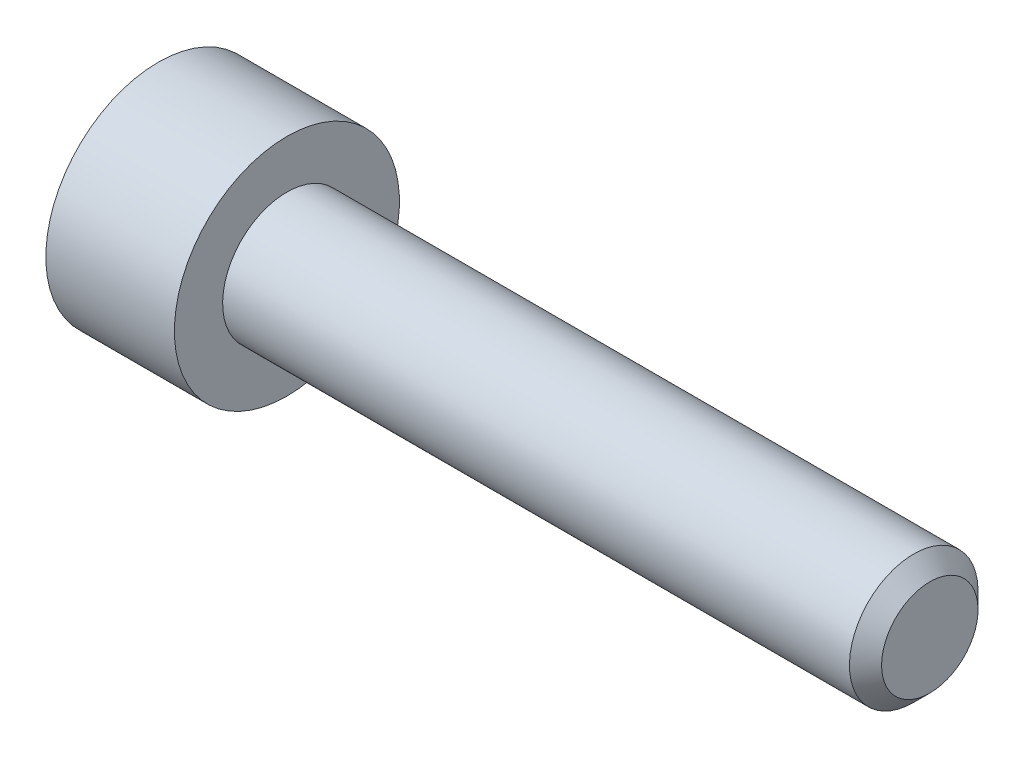
SolidWorks part; units mm, degrees
material "市購件"
ref_plane "前基準面" through (0, 0, 0) normal (0, 0, 1) x (1, 0, 0)
ref_plane "上基準面" through (0, 0, 0) normal (0, 1, 0) x (1, 0, 0)
ref_plane "右基準面" through (0, 0, 0) normal (1, 0, 0) x (0, 0, -1)
sketch "草圖1" plane through (0, 0, 0) normal (0, 0, 1) x (1, 0, 0)
  line L0 (-4, 0) -> (-4, 3.5)
  line L1 (-4, 3.5) -> (0, 3.5)
  line L2 (0, 3.5) -> (0, 2)
  line L3 (0, 2) -> (19.5, 2)
  line L4 (19.5, 2) -> (20, 1.5)
  line L5 (20, 1.5) -> (20, 0)
  line L6 (20, 0) -> (-4, 0)
  line L7 (20, 0) -> (-4, 0) construction
  dimension "D1" = 0.5
  dimension "D2" = 0.5
  dimension "D3" = 20
revolve "旋轉1" add sketch "草圖1" angle 360 about L7 reverse direction yes
cosmetic thread "裝飾螺紋線1" parameters "D2"=3.141
sketch "草圖2" plane through (0, 0, 0) normal (0, 0, 1) x (1, 0, 0)
  line L0 (-4, 0) -> (-4, 1.5)
  line L1 (-4, 1.5) -> (-2, 1.5)
  line L2 (-2, 1.5) -> (-1.5981, 0)
  line L3 (-1.5981, 0) -> (-4, 0)
  line L4 (-1.5981, 0) -> (-4, 0) construction
revolve "除料-旋轉1" cut sketch "草圖2" angle 360 about L4 reverse direction yes
ref_plane "平面1" through (-4, 0, 0) normal (1, 0, 0) x (0, 0, -1)
sketch "草圖3" plane through (-4, 0, 0) normal (1, 0, 0) x (0, 0, -1)
  line L0 (-1.5, 0.866) -> (-1.5, -0.866)
  line L1 (-1.5, -0.866) -> (0, -1.7321)
  line L2 (0, -1.7321) -> (1.5, -0.866)
  line L3 (1.5, -0.866) -> (1.5, 0.866)
  line L4 (1.5, 0.866) -> (0, 1.7321)
  line L5 (0, 1.7321) -> (-1.5, 0.866)
extrude "除料-伸長1" cut sketch "草圖3" along normal blind 2
ref_plane "平面2" through (16, 0, 0) normal (1, 0, 0) x (0, 0, -1)
ref_plane "screw1 XY" through (0, 0, 0) normal (1, 0, 0) x (0, 0, -1)
ref_plane "screw1 XZ" through (0, 0, 0) normal (0, -1, 0) x (-1, 0, 0)
ref_plane "screw1 YZ" through (0, 0, 0) normal (0, 0, -1) x (-1, 0, 0)
ref_axis "screw1 X" through (0, 0, 80.9) along (0, 0, -1)
ref_axis "screw1 Y" through (0, -50, 0) along (0, 1, 0)
ref_axis "screw1 Z" through (80.9, 0, 0) along (-1, 0, 0)
sketch3d "screw1"
  point P0 (0, 0, 0)
ref_plane "bolt_to_nut XY" through (16, 0, 0) normal (1, 0, 0) x (0, 0, -1)
ref_plane "bolt_to_nut XZ" through (0, 0, 0) normal (0, -1, 0) x (-1, 0, 0)
ref_plane "bolt_to_nut YZ" through (0, 0, 0) normal (0, 0, -1) x (-1, 0, 0)
ref_axis "bolt_to_nut X" through (16, 0, 80.9) along (0, 0, -1)
ref_axis "bolt_to_nut Y" through (16, -50, 0) along (0, 1, 0)
ref_axis "bolt_to_nut Z" through (80.9, 0, 0) along (-1, 0, 0)
sketch3d "bolt_to_nut"
  point P0 (16, 0, 0)
